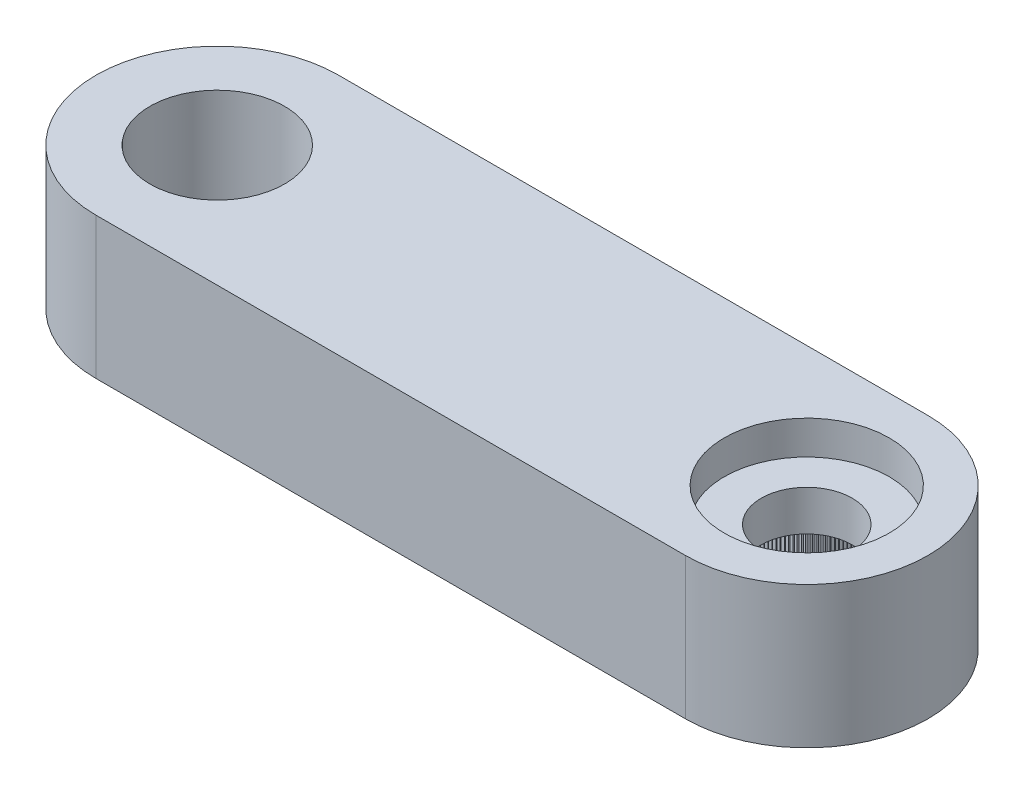
SolidWorks part; units mm, degrees
ref_plane "Front Plane" through (0, 0, 0) normal (0, 0, 1) x (1, 0, 0)
ref_plane "Top Plane" through (0, 0, 0) normal (0, 1, 0) x (1, 0, 0)
ref_plane "Right Plane" through (0, 0, 0) normal (1, 0, 0) x (0, 0, -1)
sketch "Sketch2" plane through (0, 0, 0) normal (0, 0, 1) x (1, 0, 0)
  line L0 (0, 0) -> (0, 4.6648) construction
  line L1 (3.6, 4.2) -> (3.6, 0)
  line L2 (3.6, 0) -> (2.25, 0)
  line L3 (2.25, 0) -> (2.25, 2)
  line L4 (2.25, 2) -> (1.35, 2)
  line L5 (1.35, 2) -> (1.35, 3.2)
  line L7 (1.35, 3.2) -> (2.45, 3.2)
  line L8 (2.45, 3.2) -> (2.45, 4.2)
  line L9 (2.45, 4.2) -> (3.6, 4.2)
  dimension "D1" = 3.6
  dimension "D2" = 4.2
  dimension "D3" = 2.45
  dimension "D4" = 1.35
  dimension "D5" = 1
  dimension "D6" = 2
  dimension "D7" = 2.25
revolve "Revolve1" add sketch "Sketch2" angle 360 about L0
sketch "Sketch3" plane through (0, 2, 0) normal (0, -1, 0) x (1, 0, 0)
  line L0 (-0.05, 2.2494) -> (0, 2.1494)
  line L1 (0, 2.1494) -> (0.05, 2.2494)
  circle A0 centre (0, 0) radius 2.25 construction
  circle A1 centre (0, 0) radius 2.25
  dimension "D1" = 0.1
  dimension "D2" = 0.1
extrude "Boss-Extrude1" add sketch "Sketch3" along normal up to surface (2 mm away) contours A0 L0 region at (0, 2, 2.2164) up to face at (0, 0, -3.6)
pattern_circular "CirPattern1" count 150 over 360 about axis through (0, 2, 0) along (0, -1, 0) of "Boss-Extrude1"
sketch "Sketch4" plane through (0, 4.2, 0) normal (0, 1, 0) x (1, 0, 0)
  line L0 (0, 3.6) -> (-17.5, 3.6)
  line L2 (-17.5, -3.6) -> (0, -3.6)
  circle A0 centre (0, 0) radius 3.6 construction
  circle A2 centre (-17.5, 0) radius 2
  arc A3 (0, 3.6) -> (0, -3.6) centre (0, 0) ccw
  arc A6 (-17.5, 3.6) -> (-17.5, -3.6) centre (-17.5, 0) ccw
  point P13 (-20, 3.6)
  dimension "D2" = 4
  dimension "D1" = 20
extrude "Boss-Extrude2" add sketch "Sketch4" against normal up to surface (4.2 mm away)
